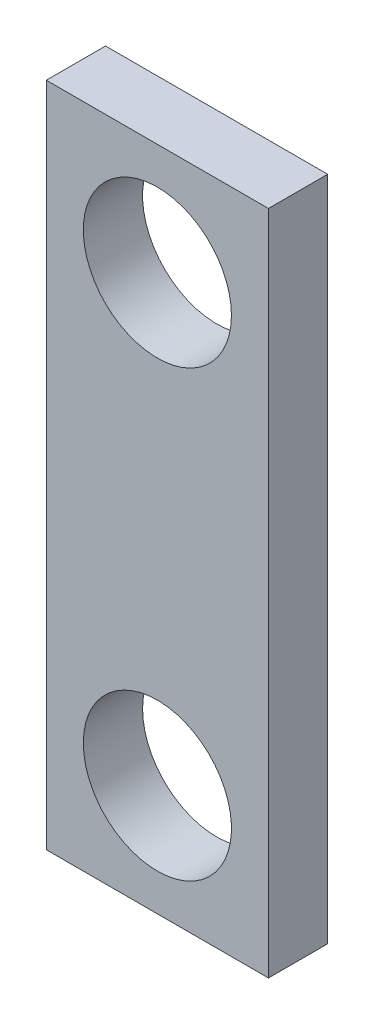
SolidWorks part; units mm, degrees
ref_plane "Front Plane" through (0, 0, 0) normal (0, 0, 1) x (1, 0, 0)
ref_plane "Top Plane" through (0, 0, 0) normal (0, 1, 0) x (1, 0, 0)
ref_plane "Right Plane" through (0, 0, 0) normal (1, 0, 0) x (0, 0, -1)
sketch "Sketch1" plane through (0, 0, 0) normal (0, 0, 1) x (1, 0, 0)
  line L0 (0, -180.975) -> (0, -219.075) construction
  line L1 (0, -200.025) -> (-9.525, -200.025) construction
  line L2 (-9.525, -228.6) -> (9.525, -228.6)
  line L3 (-9.525, -228.6) -> (-9.525, -171.45)
  line L4 (-9.525, -171.45) -> (9.525, -171.45)
  line L5 (9.525, -228.6) -> (9.525, -171.45)
  line L6 (-9.525, -228.6) -> (9.525, -171.45) construction
  line L7 (-9.525, -171.45) -> (9.525, -228.6) construction
  circle A0 centre (0, -180.975) radius 3.175 construction
  circle A1 centre (0, -200.025) radius 3.175 construction
  circle A2 centre (0, -180.975) radius 6.35
  circle A3 centre (0, -219.075) radius 3.175 construction
  circle A4 centre (0, -219.075) radius 6.35
  dimension "D1" = 6.35
  dimension "D2" = 6.35
  dimension "D3" = 19.05
  dimension "D6" = 12.7
  dimension "D4" = 19.05
  dimension "D5" = 57.15
extrude "Boss-Extrude2" add sketch "Sketch1" along normal blind 5.08
